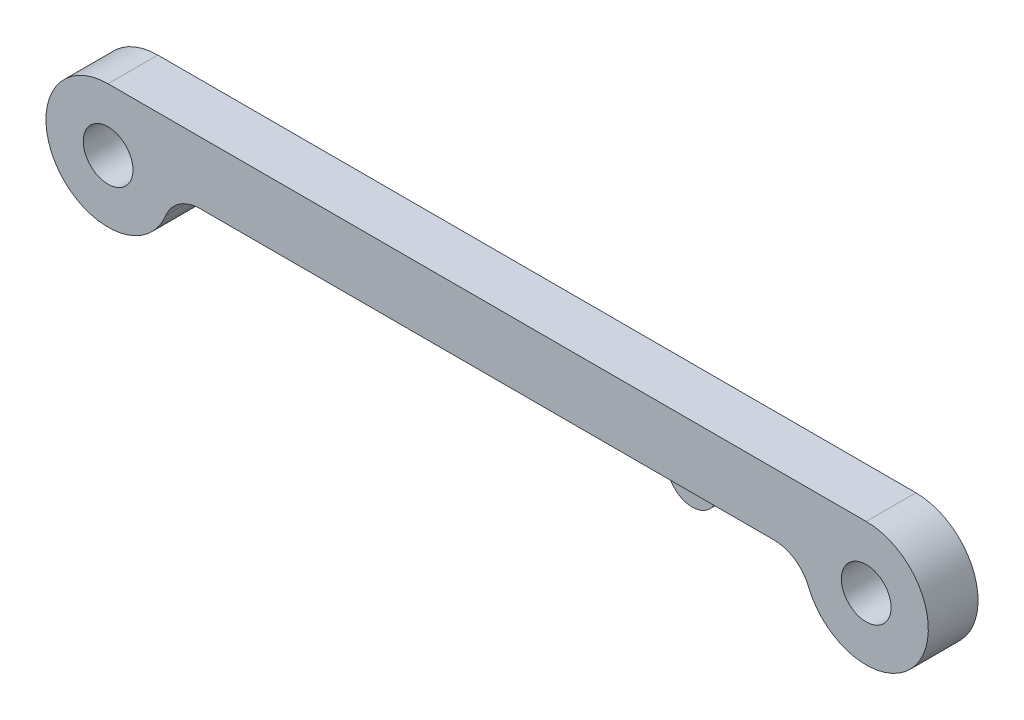
SolidWorks part; units mm, degrees
ref_plane "Front" through (0, 0, 0) normal (0, 0, 1) x (1, 0, 0)
ref_plane "Top" through (0, 0, 0) normal (0, 1, 0) x (1, 0, 0)
ref_plane "Right" through (0, 0, 0) normal (1, 0, 0) x (0, 0, -1)
sketch "Sketch1" plane through (0, 0, 0) normal (0, 0, 1) x (1, 0, 0)
  line L0 (-63.2211, 4.5) -> (-2.2211, 4.5)
  line L1 (-55.8049, -0.5) -> (-9.6373, -0.5)
  circle A0 centre (-63.2211, -0.5) radius 2
  circle A1 centre (-2.2211, -0.5) radius 2
  arc A2 (-63.2211, 4.5) -> (-58.586, -2.375) centre (-63.2211, -0.5) ccw
  arc A3 (-6.8563, -2.375) -> (-2.2211, 4.5) centre (-2.2211, -0.5) ccw
  arc A4 (-55.8049, -0.5) -> (-58.586, -2.375) centre (-55.8049, -3.5) ccw
  circle A5 centre (-63.2211, -0.5) radius 5 construction
  circle A6 centre (-2.2211, -0.5) radius 5 construction
  arc A7 (-9.6373, -0.5) -> (-6.8563, -2.375) centre (-9.6373, -3.5) cw
  point P5 (-6.7211, 0)
  point P12 (-58.7211, 0)
  point P16 (-58.2211, -0.5)
  dimension "D2" = 4
  dimension "D3" = 4
  dimension "D6" = 3
  dimension "D7" = 3
  dimension "D1" = 61
  dimension "D4" = 3
  dimension "D5" = 3
extrude "Boss-Extrude1" add sketch "Sketch1" along normal blind 4
sketch "Sketch3" plane through (0, 0, 4) normal (0, 0, 1) x (1, 0, 0)
  line L0 (-55.8049, -0.5) -> (-9.6373, -0.5) construction
  circle A0 centre (-17.2211, -0.5) radius 1
  circle A1 centre (-17.2211, -0.5) radius 2
  circle A2 centre (-2.2211, -0.5) radius 2 construction
  dimension "D1" = 2
  dimension "D2" = 4
  dimension "D3" = 15
extrude "Boss-Extrude3" add sketch "Sketch3" against normal blind 2 from offset 1 offset against normal yes
fillet "Fillet1" radius 1 2 edges at (-19.2211, -0.5, 2) (-15.2211, -0.5, 2)
